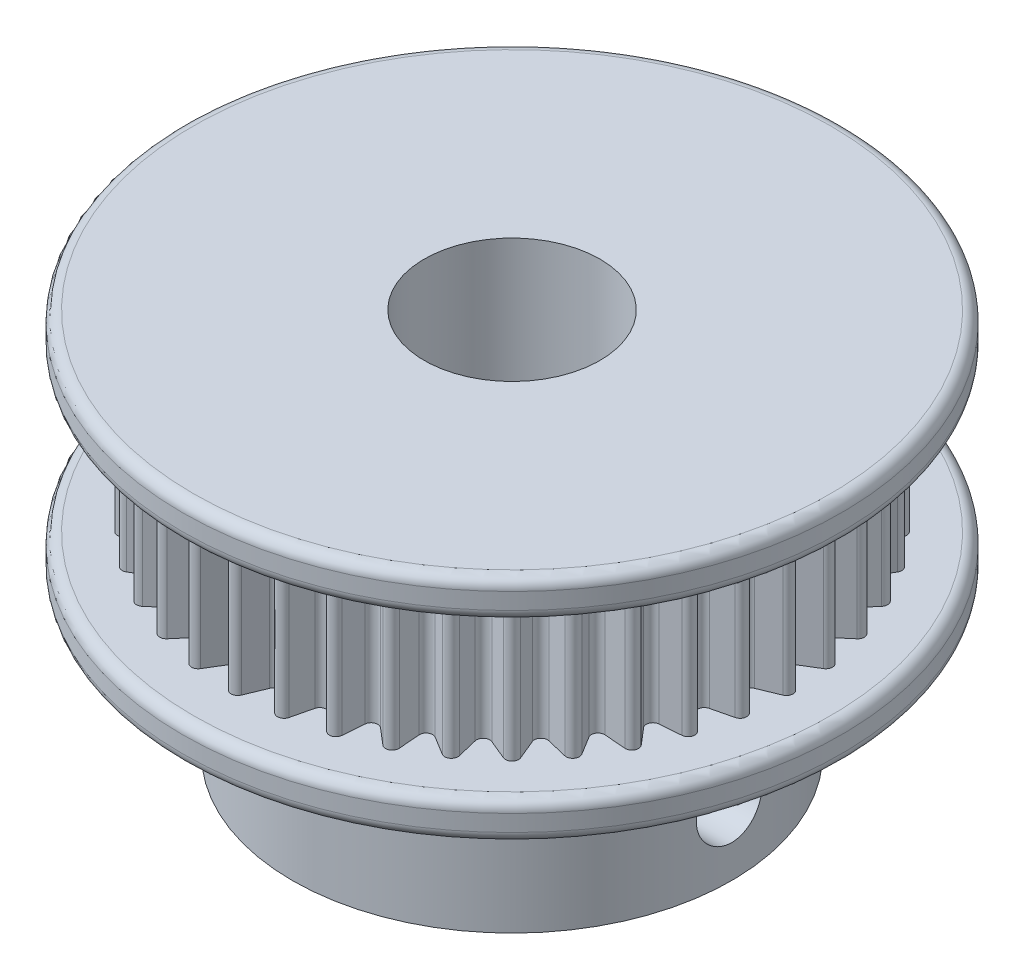
SolidWorks part; units mm, degrees
material "6063-T5"
ref_plane "Front Plane" through (0, 0, 0) normal (0, 0, 1) x (1, 0, 0)
ref_plane "Top Plane" through (0, 0, 0) normal (0, 1, 0) x (1, 0, 0)
ref_plane "Right Plane" through (0, 0, 0) normal (1, 0, 0) x (0, 0, -1)
sketch "Sketch1" plane through (0, 0, 0) normal (0, 1, 0) x (1, 0, 0)
  circle A0 centre (0, 0) radius 10
  dimension "D1" = 20
extrude "Boss-Extrude1" add sketch "Sketch1" along normal blind 7 contours A0
sketch "Sketch7" plane through (0, 7, 0) normal (0, 1, 0) x (1, 0, 0)
  circle A0 centre (0, 0) radius 15
  dimension "D1" = 30
extrude "Boss-Extrude5" add sketch "Sketch7" along normal blind 1.75
sketch "Sketch9" plane through (0, 8.75, 0) normal (0, 1, 0) x (1, 0, 0)
  line L0 (2.2448, 12.4014) -> (2.4738, 11.449)
  line L1 (3.63, 12.0689) -> (2.9936, 11.3243)
  line L2 (0, 10.95) -> (0, 0) construction
  line L3 (1.713, 10.8152) -> (0, 0) construction
  line L4 (4.1571, 11.8976) -> (4.2344, 10.9211)
  line L5 (5.4733, 11.3524) -> (4.7282, 10.7165)
  line L6 (5.9672, 11.1008) -> (5.8907, 10.1242)
  line L7 (7.1819, 10.3564) -> (6.3464, 9.845)
  line L8 (7.6302, 10.0307) -> (7.402, 9.0781)
  line L9 (8.7135, 9.1054) -> (7.8084, 8.7309)
  line L10 (9.1054, 8.7135) -> (8.7309, 7.8084)
  line L11 (10.0307, 7.6302) -> (9.0781, 7.402)
  line L12 (10.3564, 7.1819) -> (9.845, 6.3464)
  line L13 (11.1008, 5.9672) -> (10.1242, 5.8907)
  line L14 (11.3524, 5.4733) -> (10.7165, 4.7282)
  line L15 (11.8976, 4.1571) -> (10.9211, 4.2344)
  line L16 (12.0689, 3.63) -> (11.3243, 2.9936)
  line L17 (12.4014, 2.2448) -> (11.449, 2.4738)
  line L18 (12.4881, 1.6974) -> (11.6531, 1.1852)
  line L19 (12.5999, 0.2771) -> (11.6951, 0.6523)
  line L20 (12.5999, -0.2771) -> (11.6951, -0.6523)
  line L21 (12.4881, -1.6974) -> (11.6531, -1.1852)
  line L22 (12.4014, -2.2448) -> (11.449, -2.4738)
  line L23 (12.0689, -3.63) -> (11.3243, -2.9936)
  line L24 (11.8976, -4.1571) -> (10.9211, -4.2344)
  line L25 (11.3524, -5.4733) -> (10.7165, -4.7282)
  line L26 (11.1008, -5.9672) -> (10.1242, -5.8907)
  line L27 (10.3564, -7.1819) -> (9.845, -6.3464)
  line L28 (10.0307, -7.6302) -> (9.0781, -7.402)
  line L29 (9.1054, -8.7135) -> (8.7309, -7.8084)
  line L30 (8.7135, -9.1054) -> (7.8084, -8.7309)
  line L31 (7.6302, -10.0307) -> (7.402, -9.0781)
  line L32 (7.1819, -10.3564) -> (6.3464, -9.845)
  line L33 (5.9672, -11.1008) -> (5.8907, -10.1242)
  line L34 (5.4733, -11.3524) -> (4.7282, -10.7165)
  line L35 (4.1571, -11.8976) -> (4.2344, -10.9211)
  line L36 (3.63, -12.0689) -> (2.9936, -11.3243)
  line L37 (2.2448, -12.4014) -> (2.4738, -11.449)
  line L38 (1.6974, -12.4881) -> (1.1852, -11.6531)
  line L39 (0.2771, -12.5999) -> (0.6523, -11.6951)
  line L40 (-0.2771, -12.5999) -> (-0.6523, -11.6951)
  line L41 (-1.6974, -12.4881) -> (-1.1852, -11.6531)
  line L42 (-2.2448, -12.4014) -> (-2.4738, -11.449)
  line L43 (-3.63, -12.0689) -> (-2.9936, -11.3243)
  line L44 (-4.1571, -11.8976) -> (-4.2344, -10.9211)
  line L45 (-5.4733, -11.3524) -> (-4.7282, -10.7165)
  line L46 (-5.9672, -11.1008) -> (-5.8907, -10.1242)
  line L47 (-7.1819, -10.3564) -> (-6.3464, -9.845)
  line L48 (-7.6302, -10.0307) -> (-7.402, -9.0781)
  line L49 (-8.7135, -9.1054) -> (-7.8084, -8.7309)
  line L50 (-9.1054, -8.7135) -> (-8.7309, -7.8084)
  line L51 (-10.0307, -7.6302) -> (-9.0781, -7.402)
  line L52 (-10.3564, -7.1819) -> (-9.845, -6.3464)
  line L53 (-11.1008, -5.9672) -> (-10.1242, -5.8907)
  line L54 (-11.3524, -5.4733) -> (-10.7165, -4.7282)
  line L55 (-11.8976, -4.1571) -> (-10.9211, -4.2344)
  line L56 (-12.0689, -3.63) -> (-11.3243, -2.9936)
  line L57 (-12.4014, -2.2448) -> (-11.449, -2.4738)
  line L58 (-12.4881, -1.6974) -> (-11.6531, -1.1852)
  line L59 (-12.5999, -0.2771) -> (-11.6951, -0.6523)
  line L60 (-12.5999, 0.2771) -> (-11.6951, 0.6523)
  line L61 (-12.4881, 1.6974) -> (-11.6531, 1.1852)
  line L62 (-12.4014, 2.2448) -> (-11.449, 2.4738)
  line L63 (-12.0689, 3.63) -> (-11.3243, 2.9936)
  line L64 (-11.8976, 4.1571) -> (-10.9211, 4.2344)
  line L65 (-11.3524, 5.4733) -> (-10.7165, 4.7282)
  line L66 (-11.1008, 5.9672) -> (-10.1242, 5.8907)
  line L67 (-10.3564, 7.1819) -> (-9.845, 6.3464)
  line L68 (-10.0307, 7.6302) -> (-9.0781, 7.402)
  line L69 (-9.1054, 8.7135) -> (-8.7309, 7.8084)
  line L70 (-8.7135, 9.1054) -> (-7.8084, 8.7309)
  line L71 (-7.6302, 10.0307) -> (-7.402, 9.0781)
  line L72 (-7.1819, 10.3564) -> (-6.3464, 9.845)
  line L73 (-5.9672, 11.1008) -> (-5.8907, 10.1242)
  line L74 (-5.4733, 11.3524) -> (-4.7282, 10.7165)
  line L75 (-4.1571, 11.8976) -> (-4.2344, 10.9211)
  line L76 (0, 12.485) -> (0, 0) construction
  line L77 (0, 0) -> (1.9531, 12.3313) construction
  line L78 (0.2771, 12.5999) -> (0.6523, 11.6951)
  line L79 (1.6974, 12.4881) -> (1.1852, 11.6531)
  line L80 (0, 12.485) -> (1.9531, 12.3313) construction
  line L81 (0.9765, 12.4081) -> (0.9295, 11.81) construction
  line L82 (0, 12.485) -> (0, 12.785) construction
  line L83 (1.9531, 12.3313) -> (2, 12.6276) construction
  line L84 (-3.63, 12.0689) -> (-2.9936, 11.3243)
  line L154 (-2.2448, 12.4014) -> (-2.4738, 11.449)
  line L155 (-1.6974, 12.4881) -> (-1.1852, 11.6531)
  line L156 (-0.2771, 12.5999) -> (-0.6523, 11.6951)
  circle A0 centre (0, 0) radius 11.25 construction
  arc A1 (2.2448, 12.4014) -> (2, 12.6276) centre (1.9531, 12.3313) ccw
  arc A2 (2.4738, 11.449) -> (2.9936, 11.3243) centre (2.7655, 11.5192) ccw
  arc A3 (3.9508, 12.1593) -> (3.63, 12.0689) centre (3.8581, 11.8739) ccw
  arc A4 (4.1571, 11.8976) -> (3.9508, 12.1593) centre (3.8581, 11.8739) ccw
  arc A5 (4.2344, 10.9211) -> (4.7282, 10.7165) centre (4.5335, 10.9448) ccw
  arc A6 (5.8043, 11.3915) -> (5.4733, 11.3524) centre (5.6681, 11.1242) ccw
  arc A7 (5.9672, 11.1008) -> (5.8043, 11.3915) centre (5.6681, 11.1242) ccw
  arc A8 (5.8907, 10.1242) -> (6.3464, 9.845) centre (6.1898, 10.1008) ccw
  arc A9 (7.5148, 10.3433) -> (7.1819, 10.3564) centre (7.3385, 10.1006) ccw
  arc A10 (7.6302, 10.0307) -> (7.5148, 10.3433) centre (7.3385, 10.1006) ccw
  arc A11 (7.402, 9.0781) -> (7.8084, 8.7309) centre (7.6937, 9.0082) ccw
  arc A12 (9.0404, 9.0404) -> (8.7135, 9.1054) centre (8.8282, 8.8282) ccw
  arc A13 (9.1054, 8.7135) -> (9.0404, 9.0404) centre (8.8282, 8.8282) ccw
  arc A14 (8.7309, 7.8084) -> (9.0781, 7.402) centre (9.0082, 7.6937) ccw
  arc A15 (10.3433, 7.5148) -> (10.0307, 7.6302) centre (10.1006, 7.3385) ccw
  arc A16 (10.3564, 7.1819) -> (10.3433, 7.5148) centre (10.1006, 7.3385) ccw
  arc A17 (9.845, 6.3464) -> (10.1242, 5.8907) centre (10.1008, 6.1898) ccw
  arc A18 (11.3915, 5.8043) -> (11.1008, 5.9672) centre (11.1242, 5.6681) ccw
  arc A19 (11.3524, 5.4733) -> (11.3915, 5.8043) centre (11.1242, 5.6681) ccw
  arc A20 (10.7165, 4.7282) -> (10.9211, 4.2344) centre (10.9448, 4.5335) ccw
  arc A21 (12.1593, 3.9508) -> (11.8976, 4.1571) centre (11.8739, 3.8581) ccw
  arc A22 (12.0689, 3.63) -> (12.1593, 3.9508) centre (11.8739, 3.8581) ccw
  arc A23 (11.3243, 2.9936) -> (11.449, 2.4738) centre (11.5192, 2.7655) ccw
  arc A24 (12.6276, 2) -> (12.4014, 2.2448) centre (12.3313, 1.9531) ccw
  arc A25 (12.4881, 1.6974) -> (12.6276, 2) centre (12.3313, 1.9531) ccw
  arc A26 (11.6531, 1.1852) -> (11.6951, 0.6523) centre (11.81, 0.9295) ccw
  arc A27 (12.785, 0) -> (12.5999, 0.2771) centre (12.485, 0) ccw
  arc A28 (12.5999, -0.2771) -> (12.785, 0) centre (12.485, 0) ccw
  arc A29 (11.6951, -0.6523) -> (11.6531, -1.1852) centre (11.81, -0.9295) ccw
  arc A30 (12.6276, -2) -> (12.4881, -1.6974) centre (12.3313, -1.9531) ccw
  arc A31 (12.4014, -2.2448) -> (12.6276, -2) centre (12.3313, -1.9531) ccw
  arc A32 (11.449, -2.4738) -> (11.3243, -2.9936) centre (11.5192, -2.7655) ccw
  arc A33 (12.1593, -3.9508) -> (12.0689, -3.63) centre (11.8739, -3.8581) ccw
  arc A34 (11.8976, -4.1571) -> (12.1593, -3.9508) centre (11.8739, -3.8581) ccw
  arc A35 (10.9211, -4.2344) -> (10.7165, -4.7282) centre (10.9448, -4.5335) ccw
  arc A36 (11.3915, -5.8043) -> (11.3524, -5.4733) centre (11.1242, -5.6681) ccw
  arc A37 (11.1008, -5.9672) -> (11.3915, -5.8043) centre (11.1242, -5.6681) ccw
  arc A38 (10.1242, -5.8907) -> (9.845, -6.3464) centre (10.1008, -6.1898) ccw
  arc A39 (10.3433, -7.5148) -> (10.3564, -7.1819) centre (10.1006, -7.3385) ccw
  arc A40 (10.0307, -7.6302) -> (10.3433, -7.5148) centre (10.1006, -7.3385) ccw
  arc A41 (9.0781, -7.402) -> (8.7309, -7.8084) centre (9.0082, -7.6937) ccw
  arc A42 (9.0404, -9.0404) -> (9.1054, -8.7135) centre (8.8282, -8.8282) ccw
  arc A43 (8.7135, -9.1054) -> (9.0404, -9.0404) centre (8.8282, -8.8282) ccw
  arc A44 (7.8084, -8.7309) -> (7.402, -9.0781) centre (7.6937, -9.0082) ccw
  arc A45 (7.5148, -10.3433) -> (7.6302, -10.0307) centre (7.3385, -10.1006) ccw
  arc A46 (7.1819, -10.3564) -> (7.5148, -10.3433) centre (7.3385, -10.1006) ccw
  arc A47 (6.3464, -9.845) -> (5.8907, -10.1242) centre (6.1898, -10.1008) ccw
  arc A48 (5.8043, -11.3915) -> (5.9672, -11.1008) centre (5.6681, -11.1242) ccw
  arc A49 (5.4733, -11.3524) -> (5.8043, -11.3915) centre (5.6681, -11.1242) ccw
  arc A50 (4.7282, -10.7165) -> (4.2344, -10.9211) centre (4.5335, -10.9448) ccw
  arc A51 (3.9508, -12.1593) -> (4.1571, -11.8976) centre (3.8581, -11.8739) ccw
  arc A52 (3.63, -12.0689) -> (3.9508, -12.1593) centre (3.8581, -11.8739) ccw
  arc A53 (2.9936, -11.3243) -> (2.4738, -11.449) centre (2.7655, -11.5192) ccw
  arc A54 (2, -12.6276) -> (2.2448, -12.4014) centre (1.9531, -12.3313) ccw
  arc A55 (1.6974, -12.4881) -> (2, -12.6276) centre (1.9531, -12.3313) ccw
  arc A56 (1.1852, -11.6531) -> (0.6523, -11.6951) centre (0.9295, -11.81) ccw
  arc A57 (0, -12.785) -> (0.2771, -12.5999) centre (0, -12.485) ccw
  arc A58 (-0.2771, -12.5999) -> (0, -12.785) centre (0, -12.485) ccw
  arc A59 (-0.6523, -11.6951) -> (-1.1852, -11.6531) centre (-0.9295, -11.81) ccw
  arc A60 (-2, -12.6276) -> (-1.6974, -12.4881) centre (-1.9531, -12.3313) ccw
  arc A61 (-2.2448, -12.4014) -> (-2, -12.6276) centre (-1.9531, -12.3313) ccw
  arc A62 (-2.4738, -11.449) -> (-2.9936, -11.3243) centre (-2.7655, -11.5192) ccw
  arc A63 (-3.9508, -12.1593) -> (-3.63, -12.0689) centre (-3.8581, -11.8739) ccw
  arc A64 (-4.1571, -11.8976) -> (-3.9508, -12.1593) centre (-3.8581, -11.8739) ccw
  arc A65 (-4.2344, -10.9211) -> (-4.7282, -10.7165) centre (-4.5335, -10.9448) ccw
  arc A66 (-5.8043, -11.3915) -> (-5.4733, -11.3524) centre (-5.6681, -11.1242) ccw
  arc A67 (-5.9672, -11.1008) -> (-5.8043, -11.3915) centre (-5.6681, -11.1242) ccw
  arc A68 (-5.8907, -10.1242) -> (-6.3464, -9.845) centre (-6.1898, -10.1008) ccw
  arc A69 (-7.5148, -10.3433) -> (-7.1819, -10.3564) centre (-7.3385, -10.1006) ccw
  arc A70 (-7.6302, -10.0307) -> (-7.5148, -10.3433) centre (-7.3385, -10.1006) ccw
  arc A71 (-7.402, -9.0781) -> (-7.8084, -8.7309) centre (-7.6937, -9.0082) ccw
  arc A72 (-9.0404, -9.0404) -> (-8.7135, -9.1054) centre (-8.8282, -8.8282) ccw
  arc A73 (-9.1054, -8.7135) -> (-9.0404, -9.0404) centre (-8.8282, -8.8282) ccw
  arc A74 (-8.7309, -7.8084) -> (-9.0781, -7.402) centre (-9.0082, -7.6937) ccw
  arc A75 (-10.3433, -7.5148) -> (-10.0307, -7.6302) centre (-10.1006, -7.3385) ccw
  arc A76 (-10.3564, -7.1819) -> (-10.3433, -7.5148) centre (-10.1006, -7.3385) ccw
  arc A77 (-9.845, -6.3464) -> (-10.1242, -5.8907) centre (-10.1008, -6.1898) ccw
  arc A78 (-11.3915, -5.8043) -> (-11.1008, -5.9672) centre (-11.1242, -5.6681) ccw
  arc A79 (-11.3524, -5.4733) -> (-11.3915, -5.8043) centre (-11.1242, -5.6681) ccw
  arc A80 (-10.7165, -4.7282) -> (-10.9211, -4.2344) centre (-10.9448, -4.5335) ccw
  arc A81 (-12.1593, -3.9508) -> (-11.8976, -4.1571) centre (-11.8739, -3.8581) ccw
  arc A82 (-12.0689, -3.63) -> (-12.1593, -3.9508) centre (-11.8739, -3.8581) ccw
  arc A83 (-11.3243, -2.9936) -> (-11.449, -2.4738) centre (-11.5192, -2.7655) ccw
  arc A84 (-12.6276, -2) -> (-12.4014, -2.2448) centre (-12.3313, -1.9531) ccw
  arc A85 (-12.4881, -1.6974) -> (-12.6276, -2) centre (-12.3313, -1.9531) ccw
  arc A86 (-11.6531, -1.1852) -> (-11.6951, -0.6523) centre (-11.81, -0.9295) ccw
  arc A87 (-12.785, 0) -> (-12.5999, -0.2771) centre (-12.485, 0) ccw
  arc A88 (-12.5999, 0.2771) -> (-12.785, 0) centre (-12.485, 0) ccw
  arc A89 (-11.6951, 0.6523) -> (-11.6531, 1.1852) centre (-11.81, 0.9295) ccw
  arc A90 (-12.6276, 2) -> (-12.4881, 1.6974) centre (-12.3313, 1.9531) ccw
  arc A91 (-12.4014, 2.2448) -> (-12.6276, 2) centre (-12.3313, 1.9531) ccw
  arc A92 (-11.449, 2.4738) -> (-11.3243, 2.9936) centre (-11.5192, 2.7655) ccw
  arc A93 (-12.1593, 3.9508) -> (-12.0689, 3.63) centre (-11.8739, 3.8581) ccw
  arc A94 (-11.8976, 4.1571) -> (-12.1593, 3.9508) centre (-11.8739, 3.8581) ccw
  arc A95 (-10.9211, 4.2344) -> (-10.7165, 4.7282) centre (-10.9448, 4.5335) ccw
  arc A96 (-11.3915, 5.8043) -> (-11.3524, 5.4733) centre (-11.1242, 5.6681) ccw
  arc A97 (-11.1008, 5.9672) -> (-11.3915, 5.8043) centre (-11.1242, 5.6681) ccw
  arc A98 (-10.1242, 5.8907) -> (-9.845, 6.3464) centre (-10.1008, 6.1898) ccw
  arc A99 (-10.3433, 7.5148) -> (-10.3564, 7.1819) centre (-10.1006, 7.3385) ccw
  arc A100 (-10.0307, 7.6302) -> (-10.3433, 7.5148) centre (-10.1006, 7.3385) ccw
  arc A101 (-9.0781, 7.402) -> (-8.7309, 7.8084) centre (-9.0082, 7.6937) ccw
  arc A102 (-9.0404, 9.0404) -> (-9.1054, 8.7135) centre (-8.8282, 8.8282) ccw
  arc A103 (-8.7135, 9.1054) -> (-9.0404, 9.0404) centre (-8.8282, 8.8282) ccw
  arc A104 (-7.8084, 8.7309) -> (-7.402, 9.0781) centre (-7.6937, 9.0082) ccw
  arc A105 (-7.5148, 10.3433) -> (-7.6302, 10.0307) centre (-7.3385, 10.1006) ccw
  arc A106 (-7.1819, 10.3564) -> (-7.5148, 10.3433) centre (-7.3385, 10.1006) ccw
  arc A107 (-6.3464, 9.845) -> (-5.8907, 10.1242) centre (-6.1898, 10.1008) ccw
  arc A108 (-5.8043, 11.3915) -> (-5.9672, 11.1008) centre (-5.6681, 11.1242) ccw
  circle A109 centre (0, 0) radius 12.485 construction
  circle A110 centre (0, 0) radius 11.8465 construction
  arc A111 (-5.4733, 11.3524) -> (-5.8043, 11.3915) centre (-5.6681, 11.1242) ccw
  arc A112 (2, 12.6276) -> (1.6974, 12.4881) centre (1.9531, 12.3313) ccw
  arc A113 (0.6523, 11.6951) -> (1.1852, 11.6531) centre (0.9295, 11.81) ccw
  arc A114 (0.2771, 12.5999) -> (0, 12.785) centre (0, 12.485) ccw
  arc A115 (-4.7282, 10.7165) -> (-4.2344, 10.9211) centre (-4.5335, 10.9448) ccw
  arc A117 (-3.9508, 12.1593) -> (-4.1571, 11.8976) centre (-3.8581, 11.8739) ccw
  arc A118 (-3.63, 12.0689) -> (-3.9508, 12.1593) centre (-3.8581, 11.8739) ccw
  arc A120 (-2.9936, 11.3243) -> (-2.4738, 11.449) centre (-2.7655, 11.5192) ccw
  arc A121 (-2, 12.6276) -> (-2.2448, 12.4014) centre (-1.9531, 12.3313) ccw
  arc A123 (-1.6974, 12.4881) -> (-2, 12.6276) centre (-1.9531, 12.3313) ccw
  arc A124 (-1.1852, 11.6531) -> (-0.6523, 11.6951) centre (-0.9295, 11.81) ccw
  arc A126 (0, 12.785) -> (-0.2771, 12.5999) centre (0, 12.485) ccw
  point P9 (0, 0)
  point P10 (0, 0)
  point P11 (0, 0)
  point P20 (0, 0)
  point P104 (0.9765, 12.4081)
  point P418 (0, 0)
  dimension "D5" = 0.3
  dimension "D6" = 9
  dimension "D7" = 22.5
  dimension "D8" = 9
  dimension "D2" = 40
  dimension "D4" = 24.97
  dimension "D9" = 0.3
  dimension "D10" = 0.6
  dimension "D12" = 0.6
extrude "Boss-Extrude7" add sketch "Sketch9" along normal blind 7 contours A114 A126 L156 A124 L155 A123 A121 L154 A120 L84 A118 A117 L75 A115 L74 A111 A108 L73 A107 L72 A106 A105 L71 A104 L70 A103 A102 L69 A101 L68 A100 A99 L67 A98 L66 A97 A96 L65 A95 L64 A94 A93 L63 A92 L62 A91 A90 L61 A89 L60 A88 region at (0, 8.75, 0)
sketch "Sketch8" plane through (0, 15.75, 0) normal (0, 1, 0) x (1, 0, 0)
  circle A1 centre (0, 0) radius 15 construction
  circle A2 centre (0, 0) radius 15
extrude "Boss-Extrude6" add sketch "Sketch8" along normal blind 1.75
sketch "Sketch4" plane through (0, 0, 0) normal (0, -1, 0) x (1, 0, 0)
  circle A0 centre (0, 0) radius 4
  dimension "D1" = 8
extrude "Cut-Extrude4" cut sketch "Sketch4" against normal through all contours A0
sketch "Sketch5" plane through (0, 0, 0) normal (1, 0, 0) x (0, 0, -1)
  circle A0 centre (0, 3) radius 1.5
  dimension "D1" = 3
  dimension "D2" = 3
extrude "Cut-Extrude2" cut sketch "Sketch5" along normal through all
sketch "Sketch6" plane through (0, 0, 0) normal (0, 0, 1) x (1, 0, 0)
  circle A0 centre (0, 3) radius 1.5
  dimension "D1" = 3
  dimension "D2" = 3
extrude "Cut-Extrude3" cut sketch "Sketch6" against normal through all
ref_plane "Plane1" through (0, 12.25, 0) normal (0, 1, 0) x (1, 0, 0)
fillet "Fillet1" radius 0.5 4 edges at (0, 7, 15) (0, 8.75, 15) (0, 15.75, 15) (0, 17.5, 15)
sketch "Sketch10" plane through (0, 15.75, 0) normal (0, -1, 0) x (1, 0, 0)
  circle A0 centre (0, 0) radius 11.25 construction
